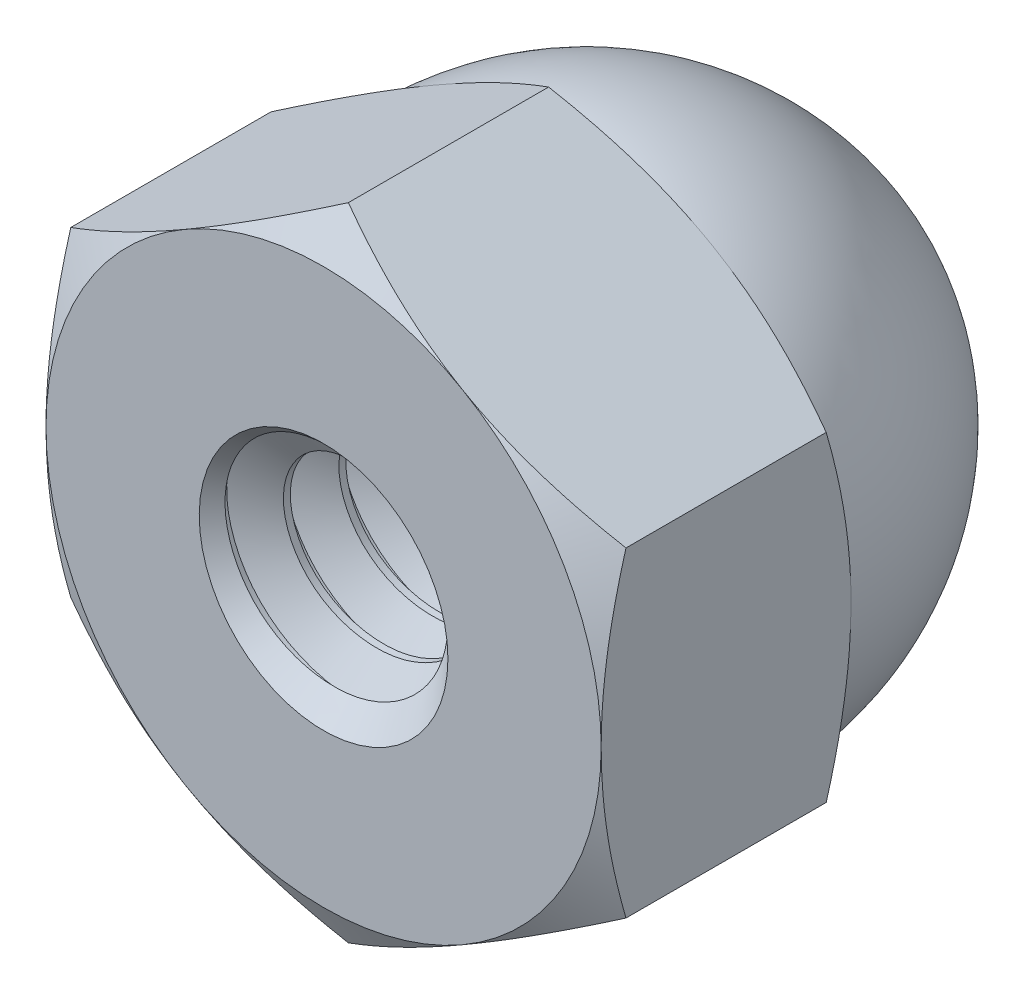
SolidWorks part; units mm, degrees
material "AISI 316 Annealed Stainless Steel Bar (SS)"
ref_plane "Front Plane" through (0, 0, 0) normal (0, 0, 1) x (1, 0, 0)
ref_plane "Top Plane" through (0, 0, 0) normal (0, 1, 0) x (1, 0, 0)
ref_plane "Right Plane" through (0, 0, 0) normal (1, 0, 0) x (0, 0, -1)
sketch "Sketch1" plane through (0, 0, 0) normal (0, 0, 1) x (1, 0, 0)
  line L1 (0, 3.6662) -> (-3.175, 1.8331)
  line L2 (-3.175, 1.8331) -> (-3.175, -1.8331)
  line L3 (-3.175, -1.8331) -> (0, -3.6662)
  line L4 (0, -3.6662) -> (3.175, -1.8331)
  line L5 (3.175, -1.8331) -> (3.175, 1.8331)
  line L6 (3.175, 1.8331) -> (0, 3.6662)
  circle A0 centre (0, 0) radius 3.175 construction
  dimension "Hex" = 6.35
extrude "Extrude1" add sketch "Sketch1" against normal blind 2.8575
sketch "Sketch2" plane through (0, 0, 0) normal (0, 0, 1) x (1, 0, 0)
  circle A0 centre (0, 0) radius 3.175 construction
  circle A1 centre (0, 0) radius 3.175
extrude "Cut-Extrude1" cut sketch "Sketch2" against normal through all draft 60 flip side to cut
sketch "Sketch3" plane through (0, 0, -2.8575) normal (0, 0, -1) x (-1, 0, 0)
  circle A1 centre (0, 0) radius 3.175
  circle A2 centre (0, 0) radius 3.175
  dimension "D1" = 0
extrude "Cut-Extrude2" cut sketch "Sketch3" against normal through all draft 60 flip side to cut
sketch "Sketch14" plane through (0, 0, 0) normal (1, 0, 0) x (0, 0, -1)
  line L0 (2.8575, 3.175) -> (2.8575, 0)
  line L1 (2.8575, 0) -> (6.35, 0)
  line L2 (2.8575, 0) -> (2.8575, 2.7496) construction
  line L3 (2.8575, 3.175) -> (12.6759, 3.175) construction
  line L6 (0, 0) -> (2.8575, 0) construction
  arc A0 (2.8575, 3.175) -> (6.35, 0) centre (2.8575, -0.3334) cw
  dimension "overall length" = 6.35
revolve "Revolve1" add sketch "Sketch14" angle 360 about L6
sketch "Sketch4" plane through (0, 0, 0) normal (0, 0, 1) x (1, 0, 0)
  circle A0 centre (0, 0) radius 1.4224
  dimension "Thread Dia" = 2.8448
extrude "Cut-Extrude3" cut sketch "Sketch4" against normal blind 3.9688
sketch "Sketch5" plane through (0, 0, 0) normal (0, 0, 1) x (1, 0, 0)
  circle A0 centre (0, 0) radius 1.4224 construction
  circle A1 centre (0, 0) radius 1.4224
sketch "Sketch15" plane through (0, 0, -3.9688) normal (0, 0, 1) x (1, 0, 0)
  circle A0 centre (0, 0) radius 1.4224 construction
  circle A1 centre (0, 0) radius 1.4224
curve "Helix/Spiral2" pitch 0.635 height 7.1437 radius 1.4224 left hand yes centre (0, 0, -3.9688) axis (0, 0, 1) start towards (0, 1, 0) parameters "pitch"=0.635
sketch "Sketch18" plane through (0, 0, 0) normal (0, 0, 1) x (1, 0, 0)
  circle A0 centre (0, 0) radius 1.4224 construction
  circle A1 centre (0, 0) radius 1.4224
sketch "Sketch16" plane through (0, 0, 0) normal (1, 0, 0) x (0, 0, -1)
  line L0 (3.9688, 1.4224) -> (4.5244, 1.4224)
  line L1 (4.5244, 1.4224) -> (4.2862, 1.01)
  line L2 (4.2862, 1.01) -> (4.2069, 1.01)
  line L3 (4.2069, 1.01) -> (3.9688, 1.4224)
  line L4 (4.2466, 1.01) -> (4.2466, 1.4224) construction
  line L5 (4.0878, 1.2162) -> (4.4053, 1.2162) construction
  line L6 (3.9688, 1.4224) -> (3.9688, -1.4224) construction
  dimension "D1" = 60
  dimension "D2" = 0.0794
  dimension "D3" = 0.3175
sweep "Sweep1" add profiles "Sketch16" path "Helix/Spiral2"
sketch "Sketch17" plane through (0, 0, 0) normal (0, 0, 1) x (1, 0, 0)
  line L6 (0, 3.6662) -> (-3.175, 1.8331)
  line L7 (-3.175, 1.8331) -> (-3.175, -1.8331)
  line L8 (-3.175, -1.8331) -> (0, -3.6662)
  line L9 (0, -3.6662) -> (3.175, -1.8331)
  line L10 (3.175, -1.8331) -> (3.175, 1.8331)
  line L11 (3.175, 1.8331) -> (0, 3.6662)
  line L12 (0, 3.6662) -> (-3.175, 1.8331)
  line L13 (-3.175, 1.8331) -> (-3.175, -1.8331)
  line L14 (-3.175, -1.8331) -> (0, -3.6662)
  line L15 (0, -3.6662) -> (3.175, -1.8331)
  line L16 (3.175, -1.8331) -> (3.175, 1.8331)
  line L17 (3.175, 1.8331) -> (0, 3.6662)
  dimension "D1" = 0
extrude "Cut-Extrude8" cut sketch "Sketch17" along normal through all
extrude "Cut-Extrude9" cut sketch "Sketch18" against normal through all draft 45
sketch "Sketch20" plane through (0, 0, 0) normal (1, 0, 0) x (0, 0, -1)
  line L0 (4.2862, 1.4224) -> (5.1075, 0)
  line L1 (3.9688, 1.4224) -> (4.2862, 1.4224)
  line L2 (3.9688, 1.4224) -> (3.9688, 0)
  line L3 (3.9688, 1.4224) -> (4.5244, 1.4224) construction
  line L4 (3.9688, 1.4224) -> (3.9688, -1.4224) construction
  line L5 (3.9688, 0) -> (5.1075, 0)
  line L6 (0, 0) -> (-3.6507, 0) construction
  dimension "D1" = 0.3175
  dimension "D2" = 60
revolve "Cut-Revolve1" cut sketch "Sketch20" angle 360 about L6
equation "\"D2@Sketch16\" = \"pitch@Helix/Spiral2\"*.125"
equation "\"D3@Sketch16\" = \"pitch@Helix/Spiral2\"*.50"
equation "\"D1@Sketch20\" = \"pitch@Helix/Spiral2\"/2"
equation "\"D3@Helix/Spiral2\" = \"Thread Depth@Cut-Extrude3\"+.125"
equation "\"Nut Height@Extrude1\" = \"overall length@Sketch14\"*.45"
